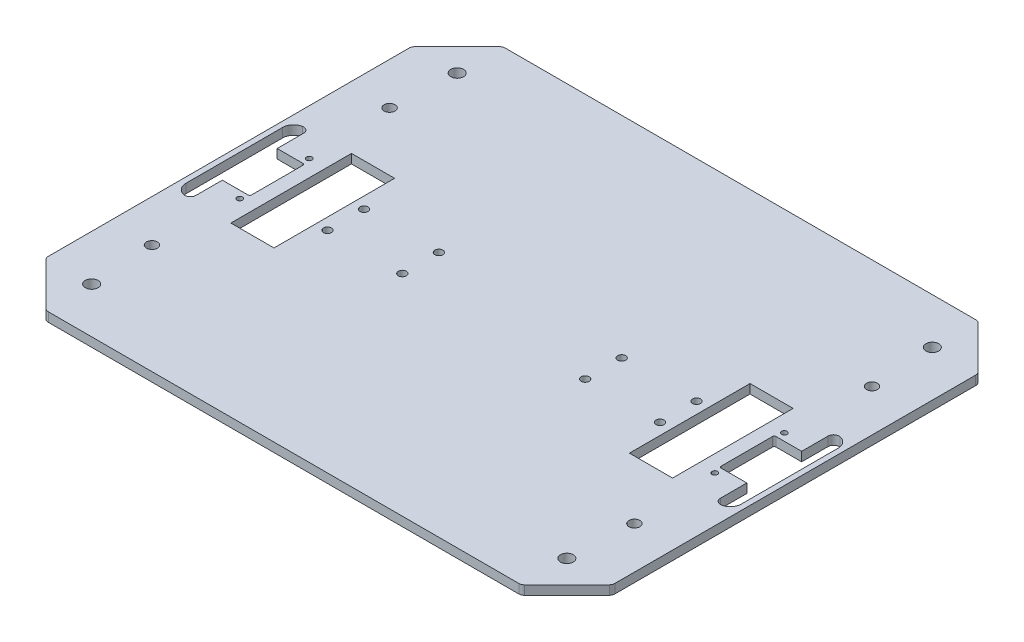
SolidWorks part; units mm, degrees
ref_plane "Plan de face" through (0, 0, 0) normal (0, 0, 1) x (1, 0, 0)
ref_plane "Plan de dessus" through (0, 0, 0) normal (0, 1, 0) x (1, 0, 0)
ref_plane "Plan de droite" through (0, 0, 0) normal (1, 0, 0) x (0, 0, -1)
sketch "Esquisse1" plane through (0, 0, 0) normal (0, 1, 0) x (1, 0, 0)
  line L0 (0, 125) -> (0, -125) construction
  line L1 (-155, 0) -> (155, 0) construction
  line L2 (-130, 125) -> (130, 125)
  line L3 (-130, -125) -> (130, -125)
  line L4 (-155, 100) -> (-155, -100)
  line L5 (155, 100) -> (155, -100)
  line L6 (-155, 100) -> (-130, 125)
  line L7 (-155, -100) -> (-130, -125)
  line L8 (130, -125) -> (155, -100)
  line L9 (130, 125) -> (155, 100)
  point P4 (0, 0)
  point P8 (0, 0)
  point P10 (0, 125)
  point P14 (0, -125)
  point P17 (-155, 0)
  point P20 (155, 0)
  dimension "D1" = 310
  dimension "D2" = 250
  dimension "D3" = 135
  dimension "D4" = 260
  dimension "D5" = 200
extrude "Boss.-Extru.1" add sketch "Esquisse1" along normal blind 5
fillet "Congé1" radius 3 8 edges at (-155, 2.5, 100) (-130, 2.5, 125) (130, 2.5, 125) (155, 2.5, 100) (155, 2.5, -100) (130, 2.5, -125) (-130, 2.5, -125) (-155, 2.5, -100)
sketch "Esquisse2" plane through (0, 5, 0) normal (0, 1, 0) x (1, 0, 0)
  line L0 (155, 0) -> (-155, 0) construction
  line L1 (-155, 98.7574) -> (-155, -98.7574) construction
  line L2 (-132, 0) -> (-132, -65) construction
  line L3 (-132, -65) -> (-155, -65) construction
  line L4 (0, 125) -> (0, -125) construction
  line L5 (-128.7574, -125) -> (128.7574, -125) construction
  circle A0 centre (-132, -65) radius 3
  circle A1 centre (-132, 65) radius 3
  circle A2 centre (132, -65) radius 3
  circle A3 centre (132, 65) radius 3
  point P6 (0, 0)
  point P18 (0, 0)
  dimension "D3" = 6
  dimension "D1" = 23
  dimension "D2" = 65
extrude "Perçage Profilé" cut sketch "Esquisse2" against normal through all
sketch "Esquisse3" plane through (0, 5, 0) normal (0, 1, 0) x (1, 0, 0)
  line L0 (-130, 19) -> (-130, -19) construction
  line L1 (155, 0) -> (-155, 0) construction
  line L2 (-155, 98.7574) -> (-155, -98.7574) construction
  line L3 (0, 125) -> (0, -125) construction
  line L4 (-128.7574, -125) -> (128.7574, -125) construction
  circle A0 centre (-130, 19) radius 1.5
  circle A1 centre (-130, -19) radius 1.5
  circle A2 centre (130, -19) radius 1.5
  circle A3 centre (130, 19) radius 1.5
  point P4 (-130, 0)
  point P10 (0, 0)
  point P16 (0, 0)
  dimension "D2" = 3
  dimension "D1" = 38
  dimension "D3" = 25
extrude "Perçage Encodeur" cut sketch "Esquisse3" against normal through all
sketch "Esquisse4" plane through (0, 5, 0) normal (0, 1, 0) x (1, 0, 0)
  line L0 (155, 0) -> (-155, 0) construction
  line L1 (143.5, -15) -> (129.5, -15)
  line L2 (-128.5, -14) -> (-128.5, 14)
  line L4 (-129.5, 15) -> (-143.5, 15)
  line L5 (-143.5, 15) -> (-143.5, 32.5)
  line L6 (-143.5, 32.5) -> (-152, 32.5)
  line L7 (-152, 32.5) -> (-152, -32.5)
  line L8 (-152, -32.5) -> (-143.5, -32.5)
  line L9 (-143.5, -32.5) -> (-143.5, -15)
  line L10 (-143.5, -15) -> (-129.5, -15)
  line L12 (-143.5, 15) -> (-143.5, -15) construction
  line L13 (143.5, -32.5) -> (143.5, -15)
  line L14 (0, 125) -> (0, -125) construction
  line L15 (-128.7574, -125) -> (128.7574, -125) construction
  line L16 (152, -32.5) -> (143.5, -32.5)
  line L27 (-155, 98.7574) -> (-155, -98.7574) construction
  line L28 (152, 32.5) -> (152, -32.5)
  line L29 (143.5, 32.5) -> (152, 32.5)
  line L30 (143.5, 15) -> (143.5, 32.5)
  line L31 (129.5, 15) -> (143.5, 15)
  line L32 (128.5, -14) -> (128.5, 14)
  arc A0 (-128.5, -14) -> (-129.5, -15) centre (-129.5, -14) cw
  arc A1 (-128.5, 14) -> (-129.5, 15) centre (-129.5, 14) ccw
  arc A2 (128.5, 14) -> (129.5, 15) centre (129.5, 14) cw
  arc A3 (128.5, -14) -> (129.5, -15) centre (129.5, -14) ccw
  point P6 (0, 0)
  point P10 (-128.5, 0)
  point P19 (-143.5, 0)
  point P25 (0, 0)
  point P28 (-128.5, 15)
  point P32 (-152, 0)
  point P45 (128.5, 15)
  point P46 (128.5, 0)
  dimension "D2" = 1
  dimension "D1" = 15
  dimension "D3" = 8.5
  dimension "D4" = 65
  dimension "D5" = 30
  dimension "D6" = 3
extrude "Poche Roue Encodeuse" cut sketch "Esquisse4" against normal through all
fillet "Congé2" radius 6 4 edges at (152, 2.5, 32.5) (152, 2.5, -32.5) (-152, 2.5, 32.5) (-152, 2.5, -32.5)
fillet "Congé3" radius 3 4 edges at (143.5, 2.5, 32.5) (143.5, 2.5, -32.5) (-143.5, 2.5, 32.5) (-143.5, 2.5, -32.5)
sketch "Esquisse5" plane through (0, 5, 0) normal (0, 1, 0) x (1, 0, 0)
  line L0 (0, 125) -> (0, -125) construction
  line L1 (128.7574, 125) -> (-128.7574, 125) construction
  line L2 (-128.7574, -125) -> (128.7574, -125) construction
  line L3 (-155, 0) -> (155, 0) construction
  line L4 (-155, 98.7574) -> (-155, -98.7574) construction
  line L5 (155, -98.7574) -> (155, 98.7574) construction
  line L7 (-50, 10) -> (-91, 10) construction
  line L8 (-50, 10) -> (-50, -10) construction
  line L9 (-50, -10) -> (-91, -10) construction
  line L10 (-91, 10) -> (-91, -10) construction
  circle A0 centre (-91, 10) radius 2.2
  circle A1 centre (-91, -10) radius 2.2
  circle A2 centre (-50, -10) radius 2.2
  circle A3 centre (-50, 10) radius 2.2
  circle A4 centre (50, 10) radius 2.2
  circle A5 centre (50, -10) radius 2.2
  circle A6 centre (91, -10) radius 2.2
  circle A7 centre (91, 10) radius 2.2
  point P16 (-50, 0)
  dimension "D4" = 4.4
  dimension "D1" = 20
  dimension "D2" = 41
  dimension "D3" = 50
extrude "Perçage Bloc Moteur" cut sketch "Esquisse5" against normal through all
sketch "Esquisse6" plane through (0, 5, 0) normal (0, 1, 0) x (1, 0, 0)
  line L0 (-91, 10) -> (-91, -10) construction
  line L1 (-120.85, 33) -> (-97.25, 33)
  line L2 (-120.85, 33) -> (-120.85, -33)
  line L3 (-120.85, -33) -> (-97.25, -33)
  line L4 (-97.25, 33) -> (-97.25, -33)
  line L5 (-91, 0) -> (-97.25, 0) construction
  line L6 (0, 125) -> (0, -125) construction
  line L7 (-128.7574, -125) -> (128.7574, -125) construction
  line L8 (120.85, -33) -> (97.25, -33)
  line L9 (97.25, 33) -> (97.25, -33)
  line L10 (120.85, 33) -> (120.85, -33)
  line L11 (120.85, 33) -> (97.25, 33)
  point P16 (0, 0)
  dimension "D1" = 23.6
  dimension "D2" = 6.25
  dimension "D3" = 66
extrude "Poche Roue Motrice" cut sketch "Esquisse6" against normal through all
sketch "Esquisse7" plane through (0, 5, 0) normal (0, 1, 0) x (1, 0, 0)
  line L0 (-155, 98.7574) -> (-155, -98.7574) construction
  line L1 (128.7574, 125) -> (-128.7574, 125) construction
  line L2 (0, 125) -> (0, -125) construction
  line L3 (-128.7574, -125) -> (128.7574, -125) construction
  line L4 (-155, 0) -> (155, 0) construction
  line L5 (155, -98.7574) -> (155, 98.7574) construction
  circle A0 centre (-130, 100) radius 3.5
  circle A1 centre (-130, -100) radius 3.5
  circle A2 centre (130, -100) radius 3.5
  circle A3 centre (130, 100) radius 3.5
  point P12 (0, 0)
  point P18 (0, 0)
  dimension "D1" = 7
  dimension "D2" = 25
  dimension "D3" = 25
extrude "Perçage Patin" cut sketch "Esquisse7" against normal through all
